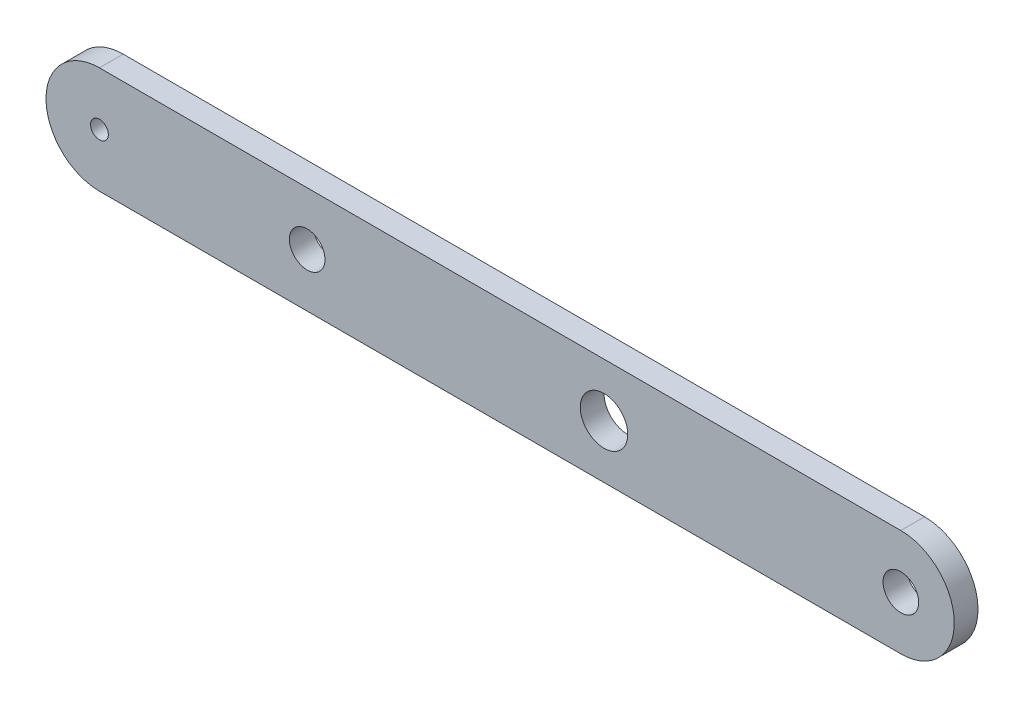
SolidWorks part; units mm, degrees
material "ﾊﾞﾙｻ"
ref_plane "正面" through (0, 0, 0) normal (0, 0, 1) x (1, 0, 0)
ref_plane "平面" through (0, 0, 0) normal (0, 1, 0) x (1, 0, 0)
ref_plane "右側面" through (0, 0, 0) normal (1, 0, 0) x (0, 0, -1)
sketch "ｽｹｯﾁ1" plane through (0, 0, 0) normal (0, 0, 1) x (1, 0, 0)
  line L0 (-35, 0) -> (100, 0) construction
  line L1 (-35, 9) -> (100, 9)
  line L2 (-35, -9) -> (100, -9)
  arc A0 (-35, 9) -> (-35, -9) centre (-35, 0) ccw
  arc A1 (100, -9) -> (100, 9) centre (100, 0) ccw
  circle A2 centre (100, 0) radius 3
  circle A3 centre (0, 0) radius 3
  circle A4 centre (-35, 0) radius 1.5
  circle A5 centre (50, 0) radius 4
  point P3 (32.5, 0)
  dimension "D2" = 6
  dimension "D3" = 9
  dimension "D4" = 6
  dimension "D5" = 3
  dimension "D7" = 8
  dimension "D1" = 100
  dimension "D6" = 35
  dimension "D8" = 50
extrude "ﾎﾞｽ - 押し出し1" add sketch "ｽｹｯﾁ1" along normal blind 4
